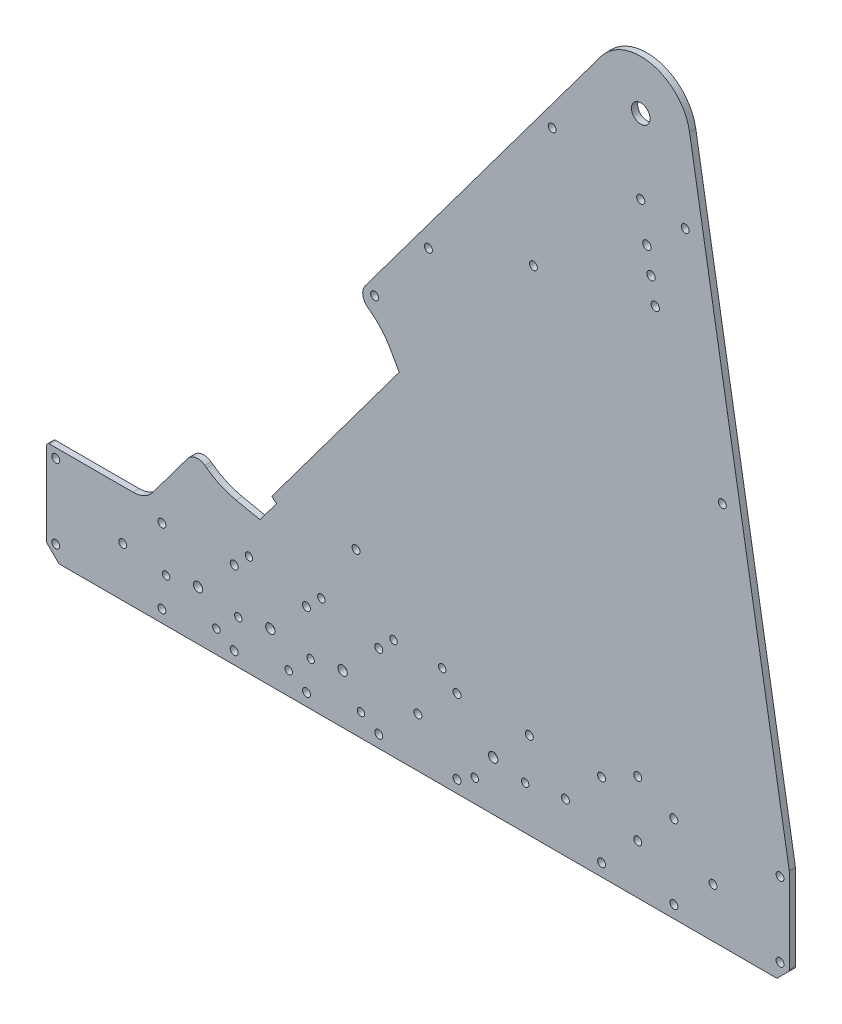
SolidWorks part; units mm, degrees
ref_plane "Front Plane" through (0, 0, 0) normal (0, 0, 1) x (1, 0, 0)
ref_plane "Top Plane" through (0, 0, 0) normal (0, 1, 0) x (1, 0, 0)
ref_plane "Right Plane" through (0, 0, 0) normal (1, 0, 0) x (0, 0, -1)
sketch "Sketch1" plane through (0, 0, 0) normal (0, 0, 1) x (1, 0, 0)
  line L1 (0, 0) -> (381, 0)
  line L2 (0, 0) -> (0, 50.8)
  line L4 (381, 0) -> (381, 50.8)
  line L5 (381, 50.8) -> (329.8448, 353.4827)
  line L6 (0, 50.8) -> (44.4242, 50.8)
  line L7 (54.6089, 55.913) -> (76.2, 84.8968)
  line L9 (115.5039, 84.5109) -> (180.9171, 172.3212)
  line L11 (159.6567, 196.9283) -> (284.4306, 364.4239)
  line L12 (115.5039, 84.5109) -> (118.05, 82.6142)
  line L13 (118.05, 82.6142) -> (109.5147, 71.1564)
  line L14 (159.6567, 196.9283) -> (172.3875, 187.4446)
  line L15 (172.3875, 187.4446) -> (180.9171, 172.3212)
  line L16 (76.2, 84.8968) -> (88.9309, 75.4131)
  line L17 (88.9309, 75.4131) -> (109.5147, 71.1564)
  line L18 (172.3875, 187.4446) -> (88.9309, 75.4131) construction
  arc A0 (284.4306, 364.4239) -> (329.8448, 353.4827) centre (304.8, 349.25) cw
  arc A1 (44.4242, 50.8) -> (54.6089, 55.913) centre (44.4242, 63.5) ccw
  point P11 (50.8, 50.8)
  point P18 (179.5094, 182.0689)
  point P20 (85.9326, 77.6466)
  point P21 (110.1624, 72.0259)
  point P23 (88.1081, 76.026)
  point P24 (180.9729, 172.3961)
  point P25 (86.3847, 77.3098)
  point P26 (180.7546, 172.103)
  dimension "D4" = 349.25
  dimension "D7" = 12.7
  dimension "D5" = 25.4
  dimension "D1" = 50.8
  dimension "D2" = 381
  dimension "D3" = 76.2
  dimension "D6" = 50.8
  dimension "D8" = 123.825
  dimension "D9" = 139.7
  dimension "D10" = 15.875
  dimension "D11" = 31.75
  dimension "D12" = 76.2
  dimension "D13" = 3.175
  dimension "D14" = 14.2875
  dimension "D15" = 115
extrude "Boss-Extrude1" add sketch "Sketch1" along normal blind 3.175
sketch "Sketch2" plane through (0, 0, 3.175) normal (0, 0, 1) x (1, 0, 0)
  line L1 (190.5, 50.8) -> (190.5, 0) construction
  line L3 (0, 0) -> (381, 0) construction
  line L5 (0, 6.35) -> (0, 0)
  line L6 (0, 50.8) -> (0, 0) construction
  line L7 (0, 0) -> (6.35, 0)
  line L8 (6.35, 0) -> (0, 6.35)
  line L9 (381, 0) -> (374.65, 0)
  line L10 (374.65, 0) -> (381, 6.35)
  line L11 (381, 6.35) -> (381, 0)
  circle A19 centre (4.7625, 46.0375) radius 2.032
  circle A20 centre (4.7625, 7.9375) radius 2.032
  circle A21 centre (376.2375, 7.9375) radius 2.032
  circle A22 centre (376.2375, 46.0375) radius 2.032
  dimension "D21" = 6.35
  dimension "D27" = 4.064
  dimension "D4" = 46.0375
  dimension "D22" = 6.35
  dimension "D25" = 4.7625
  dimension "D28" = 7.9375
extrude "Cut-Extrude1" cut sketch "Sketch2" against normal up to next
sketch "Sketch5" plane through (0, 0, 3.175) normal (0, 0, 1) x (1, 0, 0)
  line L0 (151.892, 25.4) -> (229.108, 25.4) construction
  line L1 (229.108, 25.4) -> (341.884, 25.4) construction
  circle A0 centre (39.116, 25.4) radius 2.032
  circle A1 centre (59.182, 6.35) radius 2.032
  circle A2 centre (59.182, 44.45) radius 2.032
  circle A3 centre (96.266, 44.45) radius 2.032
  circle A4 centre (133.35, 44.45) radius 2.032
  circle A5 centre (170.434, 44.45) radius 2.032
  circle A6 centre (210.566, 44.45) radius 2.032
  circle A7 centre (210.566, 6.35) radius 2.032
  circle A8 centre (170.434, 6.35) radius 2.032
  circle A9 centre (247.65, 44.45) radius 2.032
  circle A10 centre (266.192, 25.4) radius 2.032
  circle A11 centre (39.116, 25.4) radius 2.286 construction
  circle A12 centre (59.182, 44.45) radius 1.905 construction
  circle A13 centre (59.182, 6.35) radius 1.905 construction
  circle A14 centre (96.266, 44.45) radius 1.905 construction
  circle A15 centre (133.35, 44.45) radius 1.905 construction
  circle A16 centre (170.434, 44.45) radius 1.905 construction
  circle A17 centre (170.434, 6.35) radius 2.159 construction
  circle A18 centre (210.566, 6.35) radius 2.159 construction
  circle A19 centre (210.566, 44.45) radius 1.905 construction
  circle A20 centre (247.65, 44.45) radius 1.905 construction
  circle A21 centre (266.192, 25.4) radius 1.905 construction
  circle A22 centre (77.724, 25.4) radius 2.3813
  circle A23 centre (114.808, 25.4) radius 2.3813
  circle A24 centre (151.892, 25.4) radius 2.3813
  circle A25 centre (229.108, 25.4) radius 2.3813
  circle A26 centre (190.5, 25.4) radius 2.032
  circle A28 centre (303.276, 25.4) radius 2.032
  circle A29 centre (341.884, 25.4) radius 2.032
  circle A30 centre (77.724, 25.4) radius 7.366 construction
  circle A31 centre (114.808, 25.4) radius 7.366 construction
  circle A32 centre (151.892, 25.4) radius 7.366 construction
  circle A33 centre (229.108, 25.4) radius 7.366 construction
  dimension "D1" = 4.064
  dimension "D2" = 4.7625
  dimension "D3" = 37.084
  dimension "D4" = 38.608
  dimension "D5" = 38.608
extrude "Cut-Extrude4" cut sketch "Sketch5" against normal through all
sketch "Sketch6" plane through (0, 0, 3.175) normal (0, 0, 1) x (1, 0, 0)
  line L0 (6.35, 0) -> (374.65, 0) construction
  line L1 (266.192, 25.4) -> (303.276, 25.4) construction
  line L2 (284.734, 6.35) -> (284.734, 44.45) construction
  line L3 (151.892, 25.4) -> (114.808, 25.4) construction
  line L4 (114.808, 25.4) -> (77.724, 25.4) construction
  circle A0 centre (284.734, 44.45) radius 2.032
  circle A1 centre (284.734, 6.35) radius 2.032
  circle A2 centre (321.818, 6.35) radius 2.032
  circle A3 centre (321.818, 44.45) radius 2.032
  circle A4 centre (96.266, 6.35) radius 2.032
  circle A5 centre (133.35, 6.35) radius 2.032
  circle A6 centre (303.276, 53.975) radius 2.032
  arc A7 (304.329, 52.3875) -> (302.223, 52.3875) centre (303.276, 53.975) ccw construction
  point P8 (284.734, 25.4)
  point P9 (284.734, 25.4)
  point P28 (96.266, 25.4)
  point P30 (133.35, 25.4)
  dimension "D1" = 4.064
  dimension "D2" = 6.35
  dimension "D3" = 37.084
extrude "Cut-Extrude5" cut sketch "Sketch6" against normal through all
sketch "Sketch3" plane through (0, 0, 3.175) normal (0, 0, 1) x (1, 0, 0)
  line L0 (76.2, 84.8968) -> (54.6089, 55.913) construction
  line L1 (381, 6.35) -> (381, 50.8) construction
  line L2 (6.35, 0) -> (374.65, 0) construction
  line L3 (304.8, 349.25) -> (304.8, 311.15) construction
  line L4 (307.9745, 292.3664) -> (304.8, 311.15) construction
  line L5 (307.9745, 292.3664) -> (310.0909, 279.8439) construction
  line L6 (310.0909, 279.8439) -> (312.2073, 267.3215) construction
  line L7 (381, 50.8) -> (329.8448, 353.4827) construction
  line L8 (76.2, 84.8968) -> (54.6089, 55.913) construction
  line L9 (0, 50.8) -> (0, 6.35) construction
  circle A0 centre (304.8, 349.25) radius 4.7625
  circle A1 centre (168.275, 200.025) radius 2.032
  circle A2 centre (158.75, 82.55) radius 2.032
  circle A3 centre (304.8, 311.15) radius 2.0955
  circle A5 centre (307.9745, 292.3664) radius 2.159
  circle A6 centre (310.0909, 279.8439) radius 2.159
  circle A7 centre (312.2073, 267.3215) radius 2.159
  circle A8 centre (327.6094, 309.5518) radius 2.032
  circle A9 centre (346.6566, 196.85) radius 2.032
  circle A10 centre (195.8987, 234.95) radius 2.032
  circle A11 centre (249.7483, 254.0902) radius 2.032
  circle A12 centre (259.3534, 320.1311) radius 2.032
  dimension "D1" = 9.525
  dimension "D3" = 4.064
  dimension "D6" = 4.064
  dimension "D11" = 4.318
  dimension "D10" = 4.191
  dimension "D13" = 4.064
  dimension "D20" = 4.064
  dimension "D4" = 222.25
  dimension "D5" = 82.55
  dimension "D7" = 19.05
  dimension "D8" = 12.7
  dimension "D9" = 38.1
  dimension "D12" = 12.7
  dimension "D14" = 9.525
  dimension "D15" = 9.525
  dimension "D16" = 114.3
  dimension "D17" = 196.85
  dimension "D18" = 6.35
  dimension "D19" = 234.95
  dimension "D21" = 57.15
  dimension "D22" = 38.1
  dimension "D23" = 53.975
  dimension "D24" = 6.35
  dimension "D25" = 200.025
  dimension "D26" = 168.275
extrude "Cut-Extrude2" cut sketch "Sketch3" against normal through all
fillet "Fillet1" radius 1.5875 6 edges at (374.65, 0, 1.5875) (381, 6.35, 1.5875) (381, 50.8, 1.5875) (6.35, 0, 1.5875) (0, 6.35, 1.5875) (0, 50.8, 1.5875)
sketch "Sketch4" plane through (0, 0, 0) normal (0, 0, -1) x (-1, 0, 0)
  circle A0 centre (-61.3181, 22.2981) radius 1.905 construction
  circle A1 centre (-87.1313, 11.606) radius 1.905 construction
  circle A2 centre (-98.4021, 22.2981) radius 1.905 construction
  circle A3 centre (-124.2153, 11.606) radius 1.905 construction
  circle A4 centre (-135.4861, 22.2981) radius 1.905 construction
  circle A5 centre (-161.2993, 11.606) radius 1.905 construction
  circle A6 centre (-245.5139, 22.2981) radius 1.905 construction
  circle A7 centre (-219.7007, 11.606) radius 1.905 construction
  circle A8 centre (-202.982, 51.9684) radius 1.905 construction
  circle A9 centre (-178.018, 51.9684) radius 1.905 construction
  circle A10 centre (-140.934, 51.9684) radius 1.905 construction
  circle A11 centre (-103.85, 51.9684) radius 1.905 construction
  circle A12 centre (-61.3181, 22.2981) radius 1.905
  circle A13 centre (-87.1313, 11.606) radius 1.905
  circle A14 centre (-98.4021, 22.2981) radius 1.905
  circle A15 centre (-124.2153, 11.606) radius 1.905
  circle A16 centre (-135.4861, 22.2981) radius 1.905
  circle A17 centre (-161.2993, 11.606) radius 1.905
  circle A18 centre (-245.5139, 22.2981) radius 1.905
  circle A19 centre (-219.7007, 11.606) radius 1.905
  circle A20 centre (-202.982, 51.9684) radius 1.905
  circle A21 centre (-178.018, 51.9684) radius 1.905
  circle A22 centre (-140.934, 51.9684) radius 1.905
  circle A23 centre (-103.85, 51.9684) radius 1.905
extrude "Cut-Extrude3" cut sketch "Sketch4" against normal up to next
fillet "Fillet2" radius 38.1 2 edges at (88.9309, 75.4131, 1.5875) (172.3875, 187.4446, 1.5875)
fillet "Fillet3" radius 6.35 2 edges at (76.2, 84.8968, 1.5875) (159.6567, 196.9283, 1.5875)
